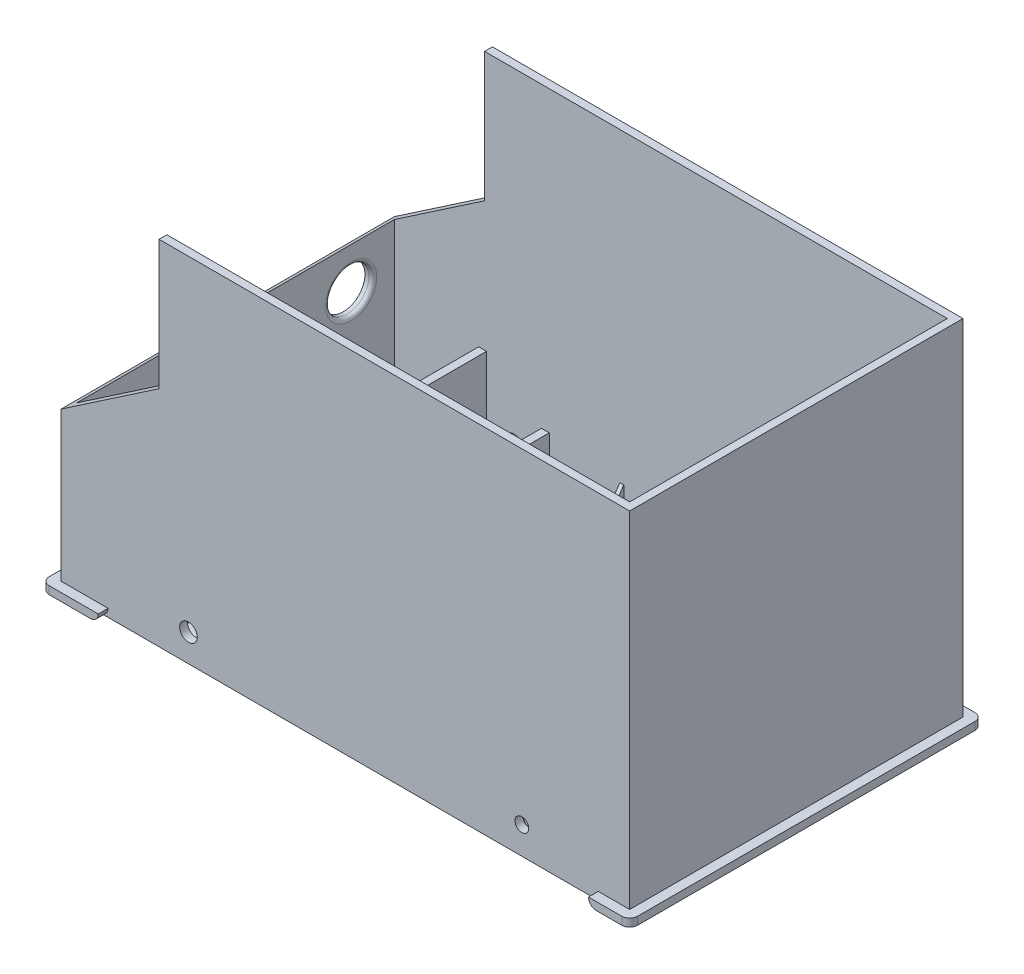
SolidWorks part; units mm, degrees
ref_plane "Face" through (0, 0, 0) normal (0, 0, 1) x (1, 0, 0)
ref_plane "Dessus" through (0, 0, 0) normal (0, 1, 0) x (1, 0, 0)
ref_plane "Droite" through (0, 0, 0) normal (1, 0, 0) x (0, 0, -1)
sketch "Esquisse1" plane through (0, 0, 0) normal (0, -1, 0) x (1, 0, 0)
  line L1 (150, 0) -> (0, 0)
  line L2 (150, 0) -> (150, 90)
  line L3 (150, 90) -> (0, 90)
  line L4 (0, 0) -> (0, 90)
extrude "Boss.-Extru.1" add sketch "Esquisse1" along normal blind 2
sketch "Esquisse2" plane through (0, 0, 0) normal (0, 1, 0) x (1, 0, 0)
  line L0 (0, -90) -> (0, 0) construction
  line L1 (2.5, -2.5) -> (147.5, -2.5)
  line L2 (2.5, -2.5) -> (2.5, -87.5)
  line L3 (2.5, -87.5) -> (147.5, -87.5)
  line L4 (147.5, -2.5) -> (147.5, -87.5)
  line L5 (150, -90) -> (0, -90) construction
  line L6 (150, 0) -> (150, -90) construction
  line L7 (0, 0) -> (150, 0) construction
  line L8 (4.5, -4.5) -> (4.5, -85.5)
  line L9 (4.5, -85.5) -> (145.5, -85.5)
  line L10 (145.5, -85.5) -> (145.5, -4.5)
  line L11 (145.5, -4.5) -> (4.5, -4.5)
  dimension "D1" = 2.5
  dimension "D2" = 2.5
  dimension "D3" = 2.5
  dimension "D4" = 2.5
  dimension "D5" = 2
  dimension "D6" = 2
  dimension "D7" = 2
  dimension "D8" = 2
extrude "Boss.-Extru.2" add sketch "Esquisse2" along normal blind 88
sketch "Esquisse3" plane through (0, 0, 0) normal (0, 1, 0) x (1, 0, 0)
  line L0 (0, -90) -> (0, 0) construction
  line L1 (0, 0) -> (150, 0) construction
  circle A0 centre (77.5, -45) radius 15
  dimension "D2" = 30
  dimension "D3" = 45
  dimension "D1" = 77.5
extrude "Enlèv. mat.-Extru.1" cut sketch "Esquisse3" against normal blind 2
sketch "Esquisse4" plane through (0, 0, 87.5) normal (0, 0, 1) x (1, 0, 0)
  line L0 (2.5, 38) -> (27.5, 55)
  line L2 (27.5, 55) -> (27.5, 88)
  line L3 (2.5, 88) -> (147.5, 88) construction
  line L4 (27.5, 88) -> (2.5, 88)
  line L5 (2.5, 88) -> (2.5, 38)
  line L7 (2.5, 88) -> (2.5, 0) construction
  line L8 (2.5, 0) -> (147.5, 0) construction
  dimension "D1" = 33
  dimension "D2" = 38
  dimension "D3" = 120
extrude "Enlèv. mat.-Extru.2" cut sketch "Esquisse4" against normal blind 90
sketch "Esquisse6" plane through (0, 0, 2.5) normal (0, 0, -1) x (-1, 0, 0)
  line L0 (0, 0) -> (-150, 0) construction
  line L1 (-2.5, 38) -> (-2.5, 0) construction
  circle A0 centre (-35, 5) radius 2.25
  dimension "D1" = 4.5
  dimension "D2" = 5
  dimension "D3" = 32.5
extrude "Enlèv. mat.-Extru.4" cut sketch "Esquisse6" against normal blind 90
fillet "Congé1" radius 2 4 edges at (150, -1, 90) (150, -1, 0) (0, -1, 90) (0, -1, 0)
sketch "Esquisse9" plane through (0, 0, 85.5) normal (0, 0, -1) x (-1, 0, 0)
  line L0 (-4.5, 0) -> (-145.5, 0) construction
  line L1 (-26, 0) -> (-28, 0)
  line L2 (-26, 0) -> (-26, 22)
  line L3 (-26, 22) -> (-28, 22)
  line L4 (-28, 0) -> (-28, 22)
  line L5 (-4.5, 39.36) -> (-4.5, 0) construction
  dimension "D1" = 21.5
  dimension "D2" = 2
  dimension "D3" = 22
extrude "Boss.-Extru.5" add sketch "Esquisse9" along normal blind 81
sketch "Esquisse11" plane through (0, 0, 0) normal (0, 1, 0) x (1, 0, 0)
  line L0 (28, -58) -> (31.5, -58)
  line L1 (28, -4.5) -> (28, -85.5) construction
  line L2 (31.5, -58) -> (31.5, -56)
  line L3 (31.5, -56) -> (28, -56)
  line L4 (28, -56) -> (28, -58)
  line L5 (28, -32) -> (31.5, -32)
  line L6 (31.5, -32) -> (31.5, -34)
  line L7 (31.5, -34) -> (28, -34)
  line L8 (28, -34) -> (28, -32)
  line L9 (37, -32) -> (37, -34)
  line L10 (37, -34) -> (44, -34)
  line L11 (44, -34) -> (44, -4.5)
  line L12 (145.5, -4.5) -> (28, -4.5) construction
  line L13 (44, -4.5) -> (42, -4.5)
  line L14 (42, -4.5) -> (42, -32)
  line L15 (42, -32) -> (37, -32)
  line L16 (37, -56) -> (44, -56)
  line L17 (44, -56) -> (44, -85.5)
  line L18 (28, -85.5) -> (145.5, -85.5) construction
  line L19 (44, -85.5) -> (42, -85.5)
  line L20 (42, -85.5) -> (42, -58)
  line L21 (42, -58) -> (37, -58)
  line L22 (37, -58) -> (37, -56)
  line L24 (148, -90) -> (2, -90) construction
  line L25 (2, 0) -> (148, 0) construction
  point P28 (29.75, -32)
  dimension "D1" = 2
  dimension "D2" = 2
  dimension "D3" = 3.5
  dimension "D4" = 3.5
  dimension "D5" = 2
  dimension "D6" = 3.5
  dimension "D7" = 32
  dimension "D8" = 32
  dimension "D9" = 32
  dimension "D10" = 32
  dimension "D11" = 2
  dimension "D12" = 2
  dimension "D13" = 2
  dimension "D14" = 2
  dimension "D15" = 14
  dimension "D16" = 14
  dimension "D17" = 7
  dimension "D18" = 7
extrude "Boss.-Extru.6" add sketch "Esquisse11" along normal blind 12
sketch "Esquisse13" plane through (2.5, 0, 0) normal (-1, 0, 0) x (0, 0, 1)
  line L0 (2.5, 38) -> (2.5, 0) construction
  line L1 (87.5, 38) -> (87.5, 0) construction
  line L2 (2.5, 38) -> (87.5, 38) construction
  circle A0 centre (15.5, 29) radius 5.5
  circle A1 centre (74.5, 29) radius 5.5
  dimension "D1" = 11
  dimension "D2" = 11
  dimension "D3" = 13
  dimension "D4" = 13
  dimension "D5" = 9
  dimension "D6" = 9
extrude "Enlèv. mat.-Extru.5" cut sketch "Esquisse13" against normal blind 2
fillet "Congé2" radius 1 2 edges at (4.5, 29, 80) (4.5, 29, 21)
sketch "Esquisse14" plane through (0, 0, 0) normal (0, 1, 0) x (1, 0, 0)
  line L0 (145.5, -85.5) -> (145.5, -4.5) construction
  line L1 (145.5, -24.7) -> (123.5, -24.7)
  line L2 (145.5, -24.7) -> (145.5, -26.7)
  line L3 (145.5, -26.7) -> (123.5, -26.7)
  line L4 (123.5, -24.7) -> (123.5, -26.7)
  line L5 (147.5, -2.5) -> (27.5, -2.5) construction
  line L6 (145.5, -67.2) -> (123.5, -67.2)
  line L7 (145.5, -67.2) -> (145.5, -69.2)
  line L8 (145.5, -69.2) -> (123.5, -69.2)
  line L9 (123.5, -67.2) -> (123.5, -69.2)
  dimension "D1" = 2
  dimension "D2" = 2
  dimension "D3" = 22
  dimension "D4" = 22
  dimension "D5" = 40.5
  dimension "D6" = 22.2
extrude "Boss.-Extru.7" add sketch "Esquisse14" along normal blind 65
sketch "Esquisse16" plane through (0, 0, 90) normal (0, 0, 1) x (1, 0, 0)
  line L0 (148, 0) -> (2, 0) construction
  line L1 (14.5, 0) -> (139.5, 0)
  line L2 (14.5, 0) -> (14.5, -2)
  line L3 (14.5, -2) -> (139.5, -2)
  line L4 (139.5, 0) -> (139.5, -2)
  line L5 (148, -2) -> (2, -2) construction
  line L6 (0, -2) -> (0, 0) construction
  dimension "D1" = 125
  dimension "D2" = 14.5
extrude "Enlèv. mat.-Extru.6" cut sketch "Esquisse16" against normal blind 2.5
sketch "Esquisse18" plane through (0, 0, 0) normal (0, 0, -1) x (-1, 0, 0)
  line L0 (-2, 0) -> (-148, 0) construction
  line L1 (-14.5, 0) -> (-140, 0)
  line L2 (-14.5, 0) -> (-14.5, -2)
  line L3 (-14.5, -2) -> (-140, -2)
  line L4 (-140, 0) -> (-140, -2)
  line L5 (-2, -2) -> (-148, -2) construction
  line L7 (-35, 5) -> (-35, -2) construction
  line L8 (-120, 0) -> (-120, -2) construction
  dimension "D1" = 20.5
  dimension "D2" = 85
  dimension "D3" = 20
extrude "Enlèv. mat.-Extru.7" cut sketch "Esquisse18" against normal blind 2.5
fillet "Congé3" radius 2 4 edges at (140, -2, 1.25) (14.5, -2, 1.25) (14.5, -2, 88.75) (139.5, -2, 88.75)
sketch "Esquisse26" plane through (0, 0, 2.5) normal (0, 0, -1) x (-1, 0, 0)
  line L2 (-147.5, 0) -> (-140, 0) construction
  circle A0 centre (-120, 5) radius 1.75
  circle A1 centre (-35, 5) radius 2.25 construction
  dimension "D3" = 3.5
  dimension "D1" = 85
  dimension "D2" = 5
extrude "Enlèv. mat.-Extru.12" cut sketch "Esquisse26" against normal blind 85
sketch "Esquisse19" plane through (28, 0, 0) normal (1, 0, 0) x (0, 0, -1)
  line L0 (-34, 0) -> (-56, 0) construction
  line L1 (-38, 0) -> (-52, 0)
  line L2 (-38, 0) -> (-38, 10)
  line L3 (-38, 10) -> (-52, 10)
  line L4 (-52, 0) -> (-52, 10)
  line L5 (-34, 12) -> (-34, 0) construction
  line L6 (-56, 12) -> (-56, 0) construction
  dimension "D1" = 10
  dimension "D2" = 4
  dimension "D3" = 4
extrude "Enlèv. mat.-Extru.8" cut sketch "Esquisse19" against normal blind 2
sketch "Esquisse20" plane through (0, 0, 0) normal (0, 1, 0) x (1, 0, 0)
  line L5 (123.1, -31.4) -> (107.5, -31.4)
  line L6 (123.1, -31.4) -> (123.1, -17.4)
  line L7 (123.1, -17.4) -> (107.5, -17.4)
  line L8 (107.5, -31.4) -> (107.5, -17.4)
  line L9 (123.1, -45.37) -> (107.5, -45.37)
  line L10 (123.1, -45.37) -> (123.1, -59.37)
  line L11 (123.1, -59.37) -> (107.5, -59.37)
  line L13 (107.5, -45.37) -> (107.5, -59.37)
  line L14 (145.5, -67.2) -> (145.5, -26.7) construction
  line L15 (44, -85.5) -> (145.5, -85.5) construction
  line L16 (145.5, -4.5) -> (44, -4.5) construction
  line L17 (145.5, -24.7) -> (145.5, -4.5) construction
  dimension "D1" = 26.13
  dimension "D2" = 14
  dimension "D3" = 15.6
  dimension "D4" = 22.4
  dimension "D5" = 14
  dimension "D6" = 15.6
  dimension "D7" = 12.9
  dimension "D8" = 22.4
extrude "Boss.-Extru.8" add sketch "Esquisse20" along normal blind 15
sketch "Esquisse23" plane through (0, 0, 24.7) normal (0, 0, -1) x (-1, 0, 0)
  line L0 (-145.5, 65) -> (-145.5, 0) construction
  line L1 (-145.5, 50) -> (-123.5, 50)
  line L2 (-145.5, 50) -> (-145.5, 20)
  line L3 (-145.5, 20) -> (-123.5, 20)
  line L4 (-123.5, 50) -> (-123.5, 20)
  line L5 (-123.5, 65) -> (-123.5, 0) construction
  line L6 (-123.5, 0) -> (-145.5, 0) construction
  line L7 (-123.5, 65) -> (-145.5, 65) construction
  dimension "D1" = 20
  dimension "D2" = 15
extrude "Enlèv. mat.-Extru.10" cut sketch "Esquisse23" against normal blind 44.5
sketch "Esquisse21" plane through (0, 15, 0) normal (0, 1, 0) x (1, 0, 0)
  line L0 (123.1, -31.4) -> (123.1, -17.4) construction
  line L1 (122.1, -19.2) -> (109.5, -19.2)
  line L2 (122.1, -19.2) -> (122.1, -29.6)
  line L3 (122.1, -29.6) -> (109.5, -29.6)
  line L4 (109.5, -19.2) -> (109.5, -29.6)
  line L5 (123.1, -17.4) -> (107.5, -17.4) construction
  line L6 (107.5, -17.4) -> (107.5, -31.4) construction
  line L7 (107.5, -31.4) -> (123.1, -31.4) construction
  line L8 (123.1, -59.37) -> (123.1, -45.37) construction
  line L9 (122.1, -47.17) -> (109.5, -47.17)
  line L10 (122.1, -47.17) -> (122.1, -57.57)
  line L11 (122.1, -57.57) -> (109.5, -57.57)
  line L12 (109.5, -47.17) -> (109.5, -57.57)
  line L13 (107.5, -59.37) -> (123.1, -59.37) construction
  line L14 (107.5, -45.37) -> (107.5, -59.37) construction
  line L15 (123.1, -45.37) -> (107.5, -45.37) construction
  dimension "D1" = 1
  dimension "D2" = 1.8
  dimension "D3" = 2
  dimension "D4" = 1.8
  dimension "D5" = 1
  dimension "D6" = 1.8
  dimension "D7" = 2
  dimension "D8" = 1.8
extrude "Enlèv. mat.-Extru.9" cut sketch "Esquisse21" against normal blind 15
sketch "Esquisse27" plane through (0, 0, 4.5) normal (0, 0, 1) x (1, 0, 0)
  circle A1 centre (120, 5) radius 3.75
  circle A2 centre (120, 5) radius 1.75 construction
  dimension "D1" = 2
extrude "Boss.-Extru.9" add sketch "Esquisse27" along normal blind 4
sketch "Esquisse29" plane through (0, 0, 8.5) normal (0, 0, 1) x (1, 0, 0)
  circle A4 centre (120, 5) radius 1.65
  dimension "D1" = 3.3
extrude "Enlèv. mat.-Extru.13" cut sketch "Esquisse29" against normal blind 4
sketch "Esquisse30" plane through (0, 0, 85.5) normal (0, 0, -1) x (-1, 0, 0)
  circle A0 centre (-120, 5) radius 3.75
  circle A1 centre (-120, 5) radius 1.75 construction
  dimension "D1" = 2
extrude "Boss.-Extru.10" add sketch "Esquisse30" along normal blind 4
sketch "Esquisse31" plane through (0, 0, 85.5) normal (0, 0, 1) x (1, 0, 0)
  circle A0 centre (120, 5) radius 1.65
  dimension "D1" = 3.3
extrude "Enlèv. mat.-Extru.14" cut sketch "Esquisse31" against normal blind 4
fillet "Congé4" radius 2 1 edges at (116.25, 5, 85.5)
fillet "Congé5" radius 2 1 edges at (123.75, 5, 4.5)
sketch "Esquisse38" plane through (0, 0, 0) normal (0, 1, 0) x (1, 0, 0)
  line L0 (44, -85.5) -> (117.1605, -85.5) construction
  line L1 (104.5, -24.5) -> (91.5, -24.5)
  line L2 (104.5, -24.5) -> (104.5, -58.5)
  line L3 (104.5, -58.5) -> (91.5, -58.5)
  line L4 (91.5, -24.5) -> (91.5, -58.5)
  line L5 (145.5, -67.2) -> (145.5, -26.7) construction
  dimension "D1" = 27
  dimension "D2" = 41
  dimension "D3" = 13
  dimension "D4" = 34
extrude "Boss.-Extru.13" add sketch "Esquisse38" along normal blind 12
sketch "Esquisse40" plane through (0, 12, 0) normal (0, 1, 0) x (1, 0, 0)
  line L0 (91.5, -24.5) -> (91.5, -58.5) construction
  line L1 (103.5, -25.5) -> (92.5, -25.5)
  line L2 (103.5, -25.5) -> (103.5, -57.5)
  line L3 (103.5, -57.5) -> (92.5, -57.5)
  line L4 (92.5, -25.5) -> (92.5, -57.5)
  line L5 (91.5, -58.5) -> (104.5, -58.5) construction
  line L6 (104.5, -24.5) -> (91.5, -24.5) construction
  dimension "D1" = 11
  dimension "D2" = 1
  dimension "D3" = 1
  dimension "D4" = 1
extrude "Enlèv. mat.-Extru.18" cut sketch "Esquisse40" against normal blind 11.99
sketch "Esquisse41" plane through (0, 0, 25.5) normal (0, 0, 1) x (1, 0, 0)
  line L0 (103.5, 12) -> (92.5, 12) construction
  line L1 (93.5, 12) -> (102.5, 12)
  line L2 (93.5, 12) -> (93.5, 0.01)
  line L3 (93.5, 0.01) -> (102.5, 0.01)
  line L4 (102.5, 12) -> (102.5, 0.01)
  line L5 (103.5, 0.01) -> (92.5, 0.01) construction
  line L6 (92.5, 0.01) -> (92.5, 12) construction
  line L7 (103.5, 0.01) -> (103.5, 12) construction
  dimension "D1" = 1
  dimension "D2" = 1
extrude "Enlèv. mat.-Extru.19" cut sketch "Esquisse41" against normal blind 1
sketch "Esquisse33" plane through (0, 0, 0) normal (0, 1, 0) x (1, 0, 0)
  line L0 (117.1605, -4.5) -> (44, -4.5) construction
  line L1 (62, -4.5) -> (63, -4.5)
  line L2 (62, -4.5) -> (62, -11.5)
  line L3 (62, -11.5) -> (63, -11.5)
  line L4 (63, -4.5) -> (63, -11.5)
  line L5 (145.5, -4.5) -> (122.8395, -4.5) construction
  line L6 (136.5, -4.5) -> (135.5, -4.5)
  line L7 (136.5, -4.5) -> (136.5, -11.5)
  line L8 (136.5, -11.5) -> (135.5, -11.5)
  line L9 (135.5, -4.5) -> (135.5, -11.5)
  line L10 (145.5, -24.7) -> (123.5, -24.7) construction
  line L11 (136.5, -24.7) -> (135.5, -24.7)
  line L12 (136.5, -24.7) -> (136.5, -17.7)
  line L13 (136.5, -17.7) -> (135.5, -17.7)
  line L14 (135.5, -24.7) -> (135.5, -17.7)
  line L15 (123.5, -69.2) -> (145.5, -69.2) construction
  line L16 (136.5, -69.2) -> (135.5, -69.2)
  line L17 (136.5, -69.2) -> (136.5, -76.2)
  line L18 (136.5, -76.2) -> (135.5, -76.2)
  line L19 (135.5, -69.2) -> (135.5, -76.2)
  line L20 (122.8395, -85.5) -> (145.5, -85.5) construction
  line L21 (136.5, -85.5) -> (135.5, -85.5)
  line L22 (136.5, -85.5) -> (136.5, -78.5)
  line L23 (136.5, -78.5) -> (135.5, -78.5)
  line L24 (135.5, -85.5) -> (135.5, -78.5)
  line L25 (44, -85.5) -> (117.1605, -85.5) construction
  line L26 (63, -85.5) -> (62, -85.5)
  line L27 (63, -85.5) -> (63, -78.5)
  line L28 (63, -78.5) -> (62, -78.5)
  line L29 (62, -85.5) -> (62, -78.5)
  line L30 (145.5, -24.7) -> (145.5, -4.5) construction
  line L31 (145.5, -85.5) -> (145.5, -69.2) construction
  line L32 (44, -34) -> (44, -4.5) construction
  line L33 (44, -85.5) -> (44, -56) construction
  line L34 (107.5, -45.37) -> (107.5, -59.37) construction
  line L35 (107.5, -54.37) -> (104.5, -54.37)
  line L36 (107.5, -54.37) -> (107.5, -52.87)
  line L37 (107.5, -52.87) -> (104.5, -52.87)
  line L38 (104.5, -54.37) -> (104.5, -52.87)
  line L39 (104.5, -58.5) -> (104.5, -24.5) construction
  line L40 (107.5, -17.4) -> (107.5, -31.4) construction
  line L41 (107.5, -29.9) -> (104.5, -29.9)
  line L42 (107.5, -29.9) -> (107.5, -28.4)
  line L43 (107.5, -28.4) -> (104.5, -28.4)
  line L44 (104.5, -29.9) -> (104.5, -28.4)
  dimension "D1" = 1
  dimension "D2" = 1
  dimension "D3" = 1
  dimension "D4" = 1
  dimension "D5" = 1
  dimension "D6" = 1
  dimension "D7" = 7
  dimension "D8" = 7
  dimension "D9" = 7
  dimension "D10" = 7
  dimension "D11" = 7
  dimension "D12" = 7
  dimension "D13" = 9
  dimension "D14" = 9
  dimension "D15" = 9
  dimension "D16" = 9
  dimension "D17" = 18
  dimension "D18" = 18
  dimension "D19" = 1.5
  dimension "D20" = 5
  dimension "D21" = 1.5
  dimension "D22" = 12.5
extrude "Boss.-Extru.11" add sketch "Esquisse33" along normal blind 10
sketch "Esquisse34" plane through (62, 0, 0) normal (-1, 0, 0) x (0, 0, 1)
  line L0 (4.5, 10) -> (11.5, 0)
  line L1 (11.5, 10) -> (11.5, 0) construction
  line L2 (11.5, 0) -> (11.5, 10)
  line L3 (11.5, 10) -> (4.5, 10)
  line L4 (4.5, 0) -> (11.5, 0) construction
  line L5 (85.5, 10) -> (78.5, 0)
  line L6 (78.5, 0) -> (85.5, 0) construction
  line L7 (78.5, 0) -> (78.5, 10)
  line L8 (78.5, 10) -> (85.5, 10)
extrude "Enlèv. mat.-Extru.15" cut sketch "Esquisse34" against normal blind 1
sketch "Esquisse35" plane through (135.5, 0, 0) normal (-1, 0, 0) x (0, 0, 1)
  line L0 (4.5, 10) -> (11.5, 0)
  line L1 (11.5, 0) -> (11.5, 10)
  line L2 (4.5, 10) -> (11.5, 10) construction
  line L3 (11.5, 10) -> (11.5, 0) construction
  line L4 (11.5, 10) -> (4.5, 10)
  line L5 (24.7, 10) -> (17.7, 0)
  line L6 (17.7, 0) -> (17.7, 10)
  line L7 (17.7, 10) -> (24.7, 10)
  line L8 (69.2, 10) -> (76.2, 0)
  line L9 (76.2, 0) -> (76.2, 10)
  line L10 (76.2, 10) -> (69.2, 10)
  line L11 (85.5, 10) -> (78.5, 0)
  line L12 (78.5, 0) -> (78.5, 10)
  line L13 (78.5, 10) -> (85.5, 10)
extrude "Enlèv. mat.-Extru.16" cut sketch "Esquisse35" against normal blind 1
sketch "Esquisse36" plane through (145.5, 0, 0) normal (-1, 0, 0) x (0, 0, 1)
  line L0 (24.7, 65) -> (24.7, 50) construction
  line L1 (24.7, 57.5) -> (19.7, 57.5)
  line L2 (24.7, 57.5) -> (24.7, 56.5)
  line L3 (24.7, 56.5) -> (19.7, 56.5)
  line L4 (19.7, 57.5) -> (19.7, 56.5)
  line L5 (69.2, 65) -> (69.2, 50) construction
  line L6 (69.2, 57.5) -> (74.2, 57.5)
  line L7 (69.2, 57.5) -> (69.2, 56.5)
  line L8 (69.2, 56.5) -> (74.2, 56.5)
  line L9 (74.2, 57.5) -> (74.2, 56.5)
  line L10 (85.5, 88) -> (4.5, 88) construction
  dimension "D1" = 5
  dimension "D2" = 5
  dimension "D3" = 1
  dimension "D4" = 1
  dimension "D5" = 30.5
extrude "Boss.-Extru.12" add sketch "Esquisse36" along normal blind 10
sketch "Esquisse37" plane through (0, 57.5, 0) normal (0, 1, 0) x (1, 0, 0)
  line L0 (145.5, -19.7) -> (135.5, -24.7)
  line L1 (135.5, -19.7) -> (135.5, -24.7)
  line L2 (135.5, -19.7) -> (145.5, -19.7)
  line L3 (145.5, -74.2) -> (135.5, -69.2)
  line L4 (135.5, -69.2) -> (135.5, -74.2)
  line L5 (135.5, -74.2) -> (145.5, -74.2)
extrude "Enlèv. mat.-Extru.17" cut sketch "Esquisse37" against normal blind 1
